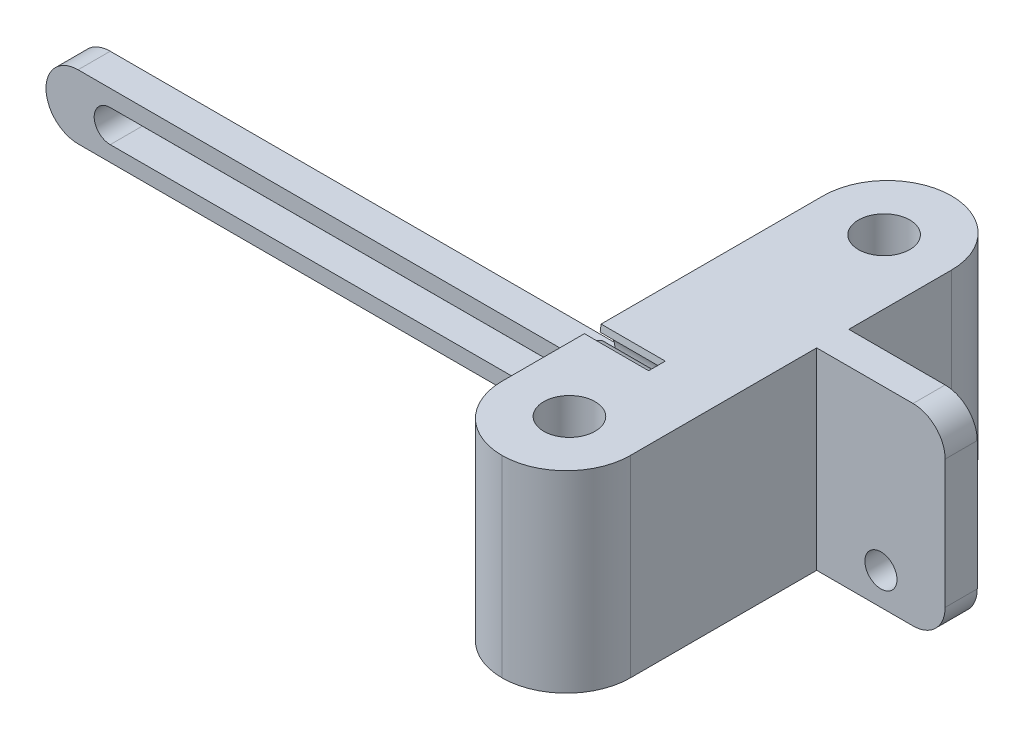
SolidWorks part; units mm, degrees
ref_plane "Front Plane" through (0, 0, 0) normal (0, 0, 1) x (1, 0, 0)
ref_plane "Top Plane" through (0, 0, 0) normal (0, 1, 0) x (1, 0, 0)
ref_plane "Right Plane" through (0, 0, 0) normal (1, 0, 0) x (0, 0, -1)
sketch "Sketch2" plane through (0, 0, 0) normal (0, 1, 0) x (1, 0, 0)
  line L1 (-3.5224, 29.7612) -> (16.4776, 29.7612)
  line L2 (-3.5224, 29.7612) -> (-3.5224, -40.2388)
  line L3 (-3.5224, -40.2388) -> (16.4776, -40.2388)
  line L4 (16.4776, 29.7612) -> (16.4776, -40.2388)
  dimension "D1" = 70
  dimension "D2" = 20
extrude "Boss-Extrude1" add sketch "Sketch2" along normal blind 30
sketch "Sketch3" plane through (0, 30, 0) normal (0, 1, 0) x (1, 0, 0)
  line L0 (16.4776, 29.7612) -> (-3.5224, 29.7612) construction
  line L1 (-3.5224, -40.2388) -> (16.4776, -40.2388) construction
  line L2 (16.4776, -40.2388) -> (16.4776, 29.7612) construction
  circle A0 centre (6.4776, 19.2612) radius 4
  circle A1 centre (6.4776, -29.7388) radius 4
  point P2 (-107.9437, 49.9012)
  point P5 (0, 0)
  dimension "D13" = 8
  dimension "D14" = 8
  dimension "D2" = 49
  dimension "D3" = 10.5
  dimension "D4" = 10.5
  dimension "D5" = 10
extrude "Cut-Extrude1" cut sketch "Sketch3" against normal blind 20
sketch "Sketch4" plane through (-3.5224, 0, 0) normal (-1, 0, 0) x (0, 0, 1)
  line L0 (8.1636, 30.0512) -> (8.1636, 15.6029) construction
  line L1 (-23.743, 30.1264) -> (40.1453, 30.1264)
  line L2 (-23.743, 30.1264) -> (-23.743, 15.6782)
  line L3 (-23.743, 15.6782) -> (40.1453, 15.6782)
  line L4 (40.1453, 30.1264) -> (40.1453, 15.6782)
  line L5 (14.95, 28.9694) -> (14.7857, 30.2017)
  line L6 (14.7857, 30.2017) -> (17.4195, 30.2017)
  line L7 (17.4195, 30.2017) -> (17.3442, 28.9224)
  circle A0 centre (16.1636, 25.6866) radius 2.5
  circle A1 centre (16.1636, 25.6866) radius 3.5
  dimension "D2" = 5
  dimension "D3" = 7
  dimension "D1" = 8
extrude "Cut-Extrude2" cut sketch "Sketch4" against normal blind 10
fillet "Fillet1" radius 10 4 edges at (-3.5224, 15, -29.7612) (16.4776, 15, -29.7612) (16.4776, 15, 40.2388) (-3.5224, 15, 40.2388)
sketch "Sketch5" plane through (-3.5224, 0, 0) normal (-1, 0, 0) x (0, 0, 1)
  line L0 (-19.7612, 30) -> (14.8126, 30) construction
  line L1 (-3.7612, 30) -> (1.2388, 30)
  line L2 (-3.7612, 30) -> (-3.7612, 0)
  line L3 (-3.7612, 0) -> (1.2388, 0)
  line L4 (1.2388, 30) -> (1.2388, 0)
  line L5 (-19.7612, 30) -> (-19.7612, 0) construction
  dimension "D1" = 5
  dimension "D2" = 30
  dimension "D3" = 0
  dimension "D4" = 16
extrude "Boss-Extrude2" add sketch "Sketch5" along normal blind 100 and the other way blind 40
sketch "Sketch6" plane through (0, 0, -3.7612) normal (0, 0, -1) x (-1, 0, 0)
  line L0 (93.5224, 4.9068) -> (-1.4776, 5) construction
  line L5 (-36.4776, 30) -> (-36.4776, 0) construction
  line L6 (103.5224, 30) -> (103.5224, 0) construction
  line L7 (3.5224, 30) -> (103.5224, 30)
  line L8 (3.5224, 30) -> (3.5224, 10)
  line L9 (3.5224, 10) -> (103.5224, 10)
  line L10 (103.5224, 30) -> (103.5224, 10)
  line L12 (93.5199, 2.4068) -> (-1.4801, 2.5)
  line L13 (93.5248, 7.4068) -> (-1.4752, 7.5)
  line L15 (-36.4776, 0) -> (-16.4776, 0) construction
  line L16 (3.5224, 0) -> (103.5224, 0) construction
  line L17 (3.5224, 30) -> (103.5224, 30) construction
  circle A0 centre (-26.4776, 5) radius 2.5
  arc A2 (93.5199, 2.4068) -> (93.5248, 7.4068) centre (93.5224, 4.9068) ccw
  arc A3 (-1.4752, 7.5) -> (-1.4801, 2.5) centre (-1.4776, 5) ccw
  point P2 (46.0224, 4.9534)
  dimension "D5" = 5
  dimension "D10" = 2.5
  dimension "D2" = 2.5
  dimension "D3" = 95
  dimension "D4" = 10
  dimension "D6" = 0
  dimension "D7" = 10
  dimension "D8" = 20
  dimension "D9" = 100
  dimension "D14" = 0
  dimension "D15" = 5
  dimension "D16" = 5
extrude "Cut-Extrude3" cut sketch "Sketch6" against normal blind 5
fillet "Fillet2" radius 5 4 edges at (36.4776, 30, -1.2612) (36.4776, 0, -1.2612) (-103.5224, 10, -1.2612) (-103.5224, 0, -1.2612)
sketch "Sketch8" plane through (16.4776, 0, 0) normal (1, 0, 0) x (0, 0, -1)
  line L0 (3.7612, 30) -> (3.7612, 0) construction
  line L1 (3.7612, 10) -> (9.7612, 10)
  line L2 (3.7612, 10) -> (3.7612, 0)
  line L3 (3.7612, 0) -> (9.7612, 0)
  line L4 (9.7612, 10) -> (9.7612, 0)
  line L5 (3.7612, 0) -> (19.7612, 0) construction
  dimension "D1" = 10
  dimension "D2" = 0
  dimension "D3" = 0
  dimension "D4" = 6
extrude "Cut-Extrude5" cut sketch "Sketch8" against normal up to next
